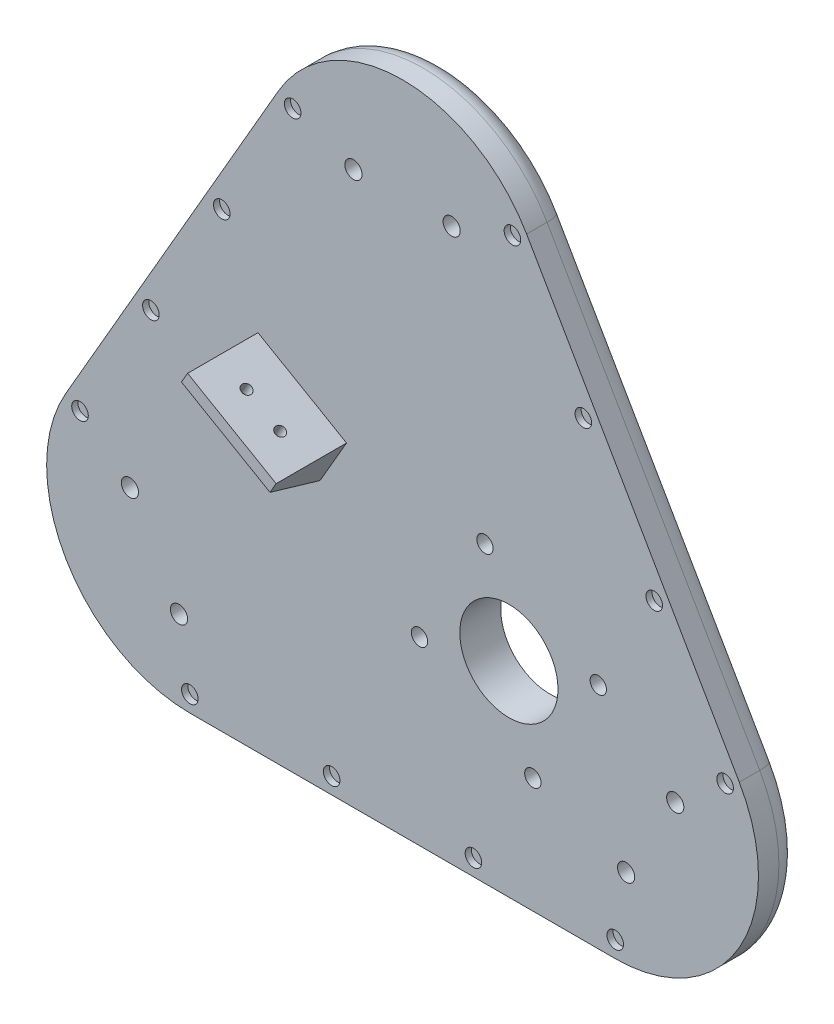
SolidWorks part; units mm, degrees
ref_plane "Plano frontal" through (0, 0, 0) normal (0, 0, 1) x (1, 0, 0)
ref_plane "Plano superior" through (0, 0, 0) normal (0, 1, 0) x (1, 0, 0)
ref_plane "Plano direito" through (0, 0, 0) normal (1, 0, 0) x (0, 0, -1)
sketch "Esboço1" plane through (0, 0, 0) normal (0, 0, 1) x (1, 0, 0)
  line L0 (0, 0) -> (0, 60) construction
  line L1 (0, 0) -> (-51.9615, -30) construction
  line L2 (0, 0) -> (51.9615, -30) construction
  line L3 (0, 0) -> (0, -52.5079) construction
  line L4 (0, 0) -> (45.4731, 26.2539) construction
  line L5 (0, 0) -> (-45.4731, 26.2539) construction
  line L6 (-12, 70) -> (12, 70) construction
  line L7 (-66.6218, -24.6077) -> (-54.6218, -45.3923) construction
  line L8 (-51.9615, -30) -> (-60.6218, -35) construction
  line L9 (0, 60) -> (0, 70) construction
  line L10 (51.9615, -30) -> (60.6218, -35) construction
  line L11 (54.6218, -45.3923) -> (66.6218, -24.6077) construction
  line L12 (31.8335, -36.8427) -> (39.8285, -22.995) construction
  line L13 (47.8235, -9.1473) -> (39.8285, -22.995) construction
  line L14 (-51.9615, -65) -> (51.9615, -65)
  line L15 (30.3109, 77.5) -> (82.2724, -12.5)
  line L16 (-30.3109, 77.5) -> (-82.2724, -12.5)
  arc A1 (51.9615, -65) -> (82.2724, -12.5) centre (51.9615, -30) ccw
  arc A2 (30.3109, 77.5) -> (-30.3109, 77.5) centre (0, 60) ccw
  arc A3 (-82.2724, -12.5) -> (-51.9615, -65) centre (-51.9615, -30) ccw
  circle A10 centre (-12, 70) radius 2.1
  circle A11 centre (-66.6218, -24.6077) radius 2.1
  circle A12 centre (12, 70) radius 2.1
  circle A13 centre (-54.6218, -45.3923) radius 2.1
  circle A24 centre (66.6218, -24.6077) radius 2.1
  circle A25 centre (54.6218, -45.3923) radius 2.1
  circle A26 centre (31.8335, -36.8427) radius 2
  circle A27 centre (25.9808, -15) radius 12
  circle A28 centre (4.138, -20.8527) radius 2
  circle A29 centre (20.128, 6.8427) radius 2
  circle A30 centre (47.8235, -9.1473) radius 2
  point P25 (0, 70)
  point P40 (51.9615, -30)
  point P41 (51.9615, -30)
  point P45 (60.6218, -35)
  point P53 (25.9808, -15)
  dimension "D3" = 24
  dimension "D5" = 70
  dimension "D9" = 4.2
  dimension "D10" = 12
  dimension "D11" = 12
  dimension "D12" = 10
  dimension "D13" = 70
  dimension "D14" = 30
  dimension "D15" = 4
  dimension "D16" = 15.99
  dimension "D17" = 10
  dimension "D18" = 24
  dimension "D19" = 4
  dimension "D1" = 120
  dimension "D2" = 120
  dimension "D4" = 60
  dimension "D6" = 120
  dimension "D7" = 120
extrude "Ressalto-extrusão1" add sketch "Esboço1" along normal blind 10
sketch "Esboço2" plane through (0, 0, 10) normal (0, 0, 1) x (1, 0, 0)
  line L0 (-56.2917, 32.5) -> (-26.005, 14.9581) construction
  line L1 (-30.3109, 77.5) -> (-82.2724, -12.5) construction
  line L2 (-36.8216, 21.2231) -> (-15.1883, 8.6932)
  line L3 (-15.1883, 8.6932) -> (-13.6847, 11.2892)
  line L4 (-13.6847, 11.2892) -> (-35.3181, 23.8191)
  line L5 (-35.3181, 23.8191) -> (-36.8216, 21.2231)
  point P7 (-26.005, 14.9581)
  dimension "D1" = 35
  dimension "D2" = 25
  dimension "D3" = 3
extrude "Ressalto-extrusão2" add sketch "Esboço2" along normal blind 17.2
sketch "Esboço3" plane through (-0.045, -0.0777, 0) normal (-0.5012, -0.8653, 0) x (0.8653, -0.5012, 0)
  line L0 (-29.9999, 27.2) -> (-29.9999, 10) construction
  line L1 (-42.4999, 27.2) -> (-17.4999, 27.2) construction
  line L2 (-42.4999, 10) -> (-17.4999, 10) construction
  line L3 (-34.7499, 19.5) -> (-25.2499, 19.5) construction
  circle A0 centre (-34.7499, 19.5) radius 1.2
  circle A1 centre (-25.2499, 19.5) radius 1.2
  point P4 (-29.9999, 19.5)
  dimension "D1" = 2.4
  dimension "D2" = 9.5
  dimension "D3" = 7.7
extrude "Corte-extrusão1" cut sketch "Esboço3" against normal up to surface (3 mm away) up to face at (-24.5014, 17.5541, 18.6)
sketch "Esboço4" plane through (-36.7766, 21.3008, 0) normal (-0.8653, 0.5012, 0) x (0, 0, 1)
  line L0 (27.2, -0.0898) -> (5.5494, -12.5898)
  line L1 (27.2, -0.0898) -> (10, -0.0898) construction
  dimension "D1" = 30
  dimension "D2" = 25
rib "Nervura1" sketch "Esboço4" sketch "Esboço4" thickness 2.5 extrusion direction parallel to sketch draft on no parameters "D1"=2.5
ref_plane "Plano1" through (-25.96, 15.0359, 0) normal (-0.8653, 0.5012, 0) x (0, 0, 1)
mirror "Espelhar1" about plane through (-25.96, 15.0359, 0) normal (-0.8653, 0.5012, 0) of "Nervura1"
sketch "Esboço5" plane through (0, 0, 10) normal (0, 0, 1) x (1, 0, 0)
  line L3 (-30.3109, 77.5) -> (-82.2724, -12.5)
  line L4 (-51.9615, -65) -> (51.9615, -65)
  line L5 (82.2724, -12.5) -> (30.3109, 77.5)
  line L6 (-30.3109, 77.5) -> (-82.2724, -12.5) construction
  line L7 (-51.9615, -65) -> (51.9615, -65) construction
  line L8 (82.2724, -12.5) -> (30.3109, 77.5) construction
  line L12 (-26.8468, 75.5) -> (-78.8083, -14.5) construction
  line L13 (-51.9615, -61) -> (51.9615, -61) construction
  line L14 (78.8083, -14.5) -> (26.8468, 75.5) construction
  arc A3 (30.3109, 77.5) -> (-30.3109, 77.5) centre (0, 60) ccw
  arc A4 (-82.2724, -12.5) -> (-51.9615, -65) centre (-51.9615, -30) ccw
  arc A5 (51.9615, -65) -> (82.2724, -12.5) centre (51.9615, -30) ccw
  arc A6 (30.3109, 77.5) -> (-30.3109, 77.5) centre (0, 60) ccw construction
  arc A7 (-82.2724, -12.5) -> (-51.9615, -65) centre (-51.9615, -30) ccw construction
  arc A8 (51.9615, -65) -> (82.2724, -12.5) centre (51.9615, -30) ccw construction
  arc A25 (26.8468, 75.5) -> (-26.8468, 75.5) centre (0, 60) ccw construction
  arc A26 (-78.8083, -14.5) -> (-51.9615, -61) centre (-51.9615, -30) ccw construction
  arc A27 (51.9615, -61) -> (78.8083, -14.5) centre (51.9615, -30) ccw construction
  circle A28 centre (-78.8083, -14.5) radius 2.025
  circle A29 centre (-51.9615, -61) radius 2.025
  circle A30 centre (26.8468, 75.5) radius 2.025
  circle A31 centre (44.1668, 45.5009) radius 2.025
  circle A32 centre (61.4868, 15.5018) radius 2.025
  circle A33 centre (78.8068, -14.4974) radius 2.025
  circle A34 centre (-61.4883, 15.4991) radius 2.025
  circle A35 centre (-44.1683, 45.4982) radius 2.025
  circle A36 centre (-26.8483, 75.4974) radius 2.025
  circle A37 centre (-17.3215, -61) radius 2.025
  circle A38 centre (17.3185, -61) radius 2.025
  circle A39 centre (51.9585, -61) radius 2.025
  dimension "D3" = 103.923
  dimension "D2" = 4.05
  dimension "D4" = 4
  dimension "D8" = 4
  dimension "D1" = 0
  dimension "D5" = 4
  dimension "D6" = 4
extrude "Corte-extrusão2" cut sketch "Esboço5" against normal blind 1.5
fillet "Filete1" radius 5 6 edges at (0, 95, 0) (56.2917, 32.5, 0) (82.2724, -47.5, 0) (0, -65, 0) (-82.2724, -47.5, 0) (-56.2917, 32.5, 0)
